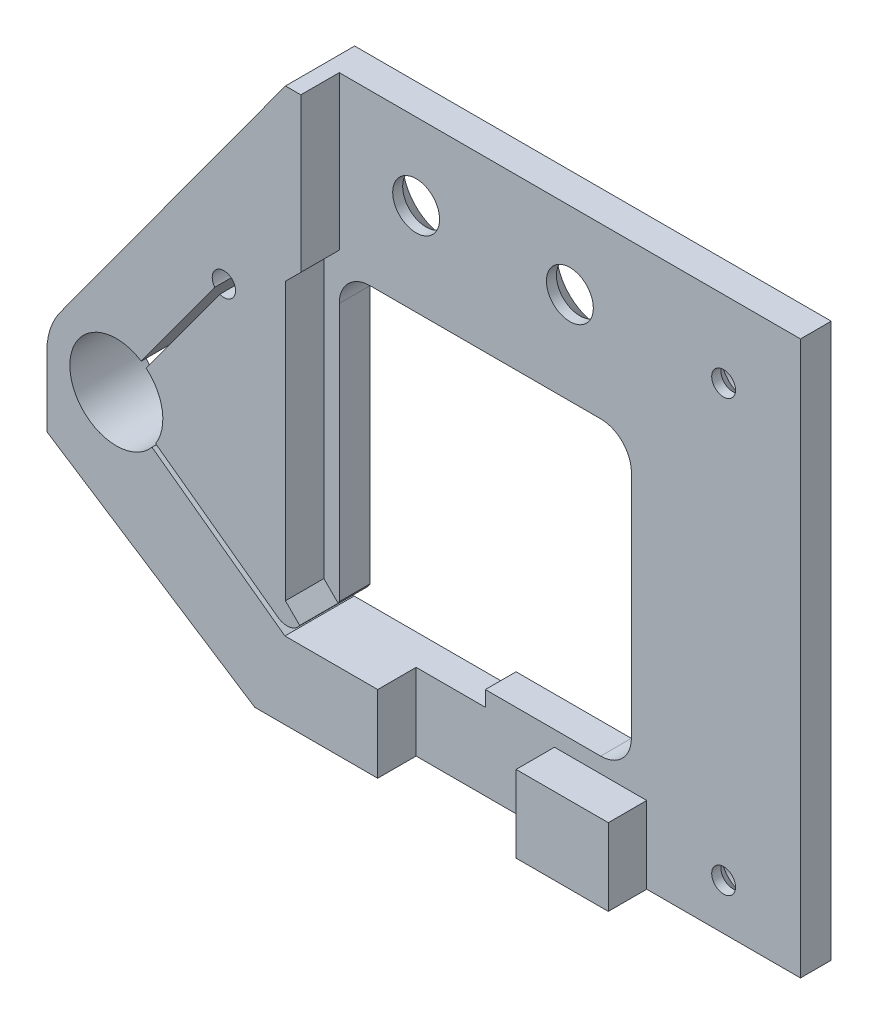
SolidWorks part; units mm, degrees
ref_plane "Front Plane" through (0, 0, 0) normal (0, 0, 1) x (1, 0, 0)
ref_plane "Top Plane" through (0, 0, 0) normal (0, 1, 0) x (1, 0, 0)
ref_plane "Right Plane" through (0, 0, 0) normal (1, 0, 0) x (0, 0, -1)
sketch "Sketch1" plane through (0, 0, 0) normal (0, 0, 1) x (1, 0, 0)
  line L0 (84, 45.5) -> (84, 24)
  line L1 (79, -14.5) -> (24, -14.5) construction
  line L2 (84, 45.5) -> (22, 45.5)
  line L3 (-9.05, 0) -> (-9.05, -8.9672)
  line L4 (22, -16.5) -> (64, -16.5) construction
  line L5 (22, -16.5) -> (22, 25.5) construction
  line L6 (64, -16.5) -> (64, 25.5) construction
  line L7 (22, 25.5) -> (64, 25.5) construction
  line L8 (84, 45.5) -> (24, 45.5) construction
  line L9 (84, -14.5) -> (84, -26.5)
  line L10 (24, 45.5) -> (24, 25.5) construction
  line L11 (24, 45.5) -> (64, 45.5) construction
  line L12 (22, -16.5) -> (64, 25.5) construction
  line L13 (64, -16.5) -> (22, 25.5) construction
  line L14 (43, 23.5) -> (43, 7.5)
  line L15 (64, 45.5) -> (64, 25.5) construction
  line L16 (24, 45.5) -> (64, 25.5) construction
  line L17 (24, 25.5) -> (64, 45.5) construction
  line L18 (24, 23.5) -> (79, 23.5) construction
  line L19 (24, 23.5) -> (24.2, -13.2184)
  line L20 (84, -26.5) -> (18, -26.5)
  line L21 (18, -26.5) -> (-9.05, -8.9672)
  line L22 (22, 45.5) -> (-7.3104, 5.3348)
  line L23 (34, 35.5) -> (54, 35.5) construction
  line L24 (84, -14.5) -> (84, 24)
  line L25 (79, -14.5) -> (79, 23.5) construction
  line L26 (74, -20.5) -> (84, -20.5) construction
  line L27 (0, 0) -> (13.9906, 19.1719) construction
  line L28 (3.8817, 4.6406) -> (13.4512, 17.7542)
  line L29 (3.2354, 5.1122) -> (12.805, 18.2258)
  line L30 (0, 0) -> (7.4321, -5.4235) construction
  line L31 (0.3231, -0.2358) -> (14.3137, 18.9361) construction
  line L32 (-0.3231, 0.2358) -> (13.6675, 19.4077) construction
  line L33 (4.6406, -3.8817) -> (21.932, -16.5)
  line L34 (5.1122, -3.2354) -> (21.0211, -14.8449)
  line L35 (24, -18.0091) -> (24, -14.5) construction
  line L36 (0.2358, 0.3231) -> (7.6679, -5.1004) construction
  line L37 (-0.2358, -0.3231) -> (7.1963, -5.7466) construction
  line L38 (43, -16.5) -> (21.932, -16.5)
  line L39 (24, 23.5) -> (43, 23.5)
  line L40 (43, 1.5) -> (43, -16.5)
  arc A0 (3.2354, 5.1122) -> (4.6406, -3.8817) centre (0, 0) ccw construction
  arc A1 (-7.3104, 5.3348) -> (-9.05, 0) centre (0, 0) ccw
  circle A2 centre (34, 35.5) radius 3.05
  arc A3 (6.3993, -6.3993) -> (-0.7722, -9.017) centre (0, 0) ccw construction
  arc A4 (43, 1.5) -> (43, 7.5) centre (43, 4.5) ccw
  circle A5 centre (54, 35.5) radius 3.05
  circle A6 centre (74, 35.5) radius 1.55
  circle A7 centre (74, -20.5) radius 1.55
  arc A8 (5.1122, -3.2354) -> (3.8817, 4.6406) centre (0, 0) ccw construction
  arc A9 (24.2, -13.2184) -> (21.0211, -14.8449) centre (22.2, -13.2293) cw
  arc A10 (13.4512, 17.7542) -> (12.805, 18.2258) centre (13.9906, 19.1719) ccw
  arc A11 (5.1122, -3.2354) -> (3.8817, 4.6406) centre (0, 0) ccw
  arc A12 (3.2354, 5.1122) -> (4.6406, -3.8817) centre (0, 0) ccw
  point P11 (0, 0)
  point P13 (9.6881, 0)
  point P17 (44, 35.5)
  dimension "D3" = 12.1
  dimension "D4" = 3
  dimension "D1" = 42
  dimension "D2" = 6
  dimension "D6" = 12
  dimension "D12" = 6.1
  dimension "D17" = 3.1
  dimension "D23" = 2
  dimension "D5" = 42
  dimension "D7" = 40
  dimension "D8" = 44
  dimension "D9" = 35.5
  dimension "D10" = 20
  dimension "D11" = 10
  dimension "D13" = 20
  dimension "D14" = 5
  dimension "D15" = 20
  dimension "D16" = 10
  dimension "D22" = 0.2
  dimension "D18" = 0.4
  dimension "D19" = 0.4
  dimension "D20" = 0.4
  dimension "D21" = 0.4
extrude "Boss-Extrude1" add sketch "Sketch1" along normal blind 9
sketch "Sketch2" plane through (0, 0, 9) normal (0, 0, 1) x (1, 0, 0)
  line L0 (24, 25.5) -> (22, 25.5)
  line L1 (22, 25.5) -> (22, -12.5)
  line L2 (64, -16.5) -> (64, -26.5)
  line L3 (26, -16.5) -> (34, -16.5)
  line L4 (22, 25.5) -> (64, -16.5) construction
  line L5 (64, 25.5) -> (22, -16.5) construction
  line L6 (64, -26.5) -> (84, -26.5)
  line L7 (18, -26.5) -> (84, -26.5) construction
  line L8 (43, 4.5) -> (43, -26.5) construction
  line L9 (22, -12.5) -> (26, -16.5)
  line L10 (34, 35.5) -> (54, 35.5) construction
  line L11 (24, 25.5) -> (24, 45.5)
  line L12 (84, -26.5) -> (84, 45.5)
  line L13 (24, 45.5) -> (84, 45.5)
  line L14 (34, -16.5) -> (34, -26.5)
  line L15 (24, 25.5) -> (64, 45.5) construction
  line L16 (24, 45.5) -> (64, 25.5) construction
  line L17 (34, -26.5) -> (52, -26.5)
  line L18 (52, -26.5) -> (52, -16.5)
  line L19 (52, -16.5) -> (64, -16.5)
  point P1 (43, 4.5)
  point P19 (44, 35.5)
  dimension "D1" = 42
  dimension "D3" = 18
  dimension "D2" = 40
extrude "Cut-Extrude1" cut sketch "Sketch2" against normal offset from surface (5 mm away) 4 up to face at (75.55, 35.5, 0)
chamfer "Chamfer2" distance 2.7 angle 45 2 edges at (37.05, 35.5, 0) (57.05, 35.5, 0)
sketch "Sketch3" plane through (0, 0, 4) normal (0, 0, 1) x (1, 0, 0)
  line L1 (24, -14.5) -> (62, -14.5)
  line L2 (24, -14.5) -> (24, 23.5)
  line L3 (24, 23.5) -> (62, 23.5)
  line L4 (62, -14.5) -> (62, 23.5)
  line L5 (24, -14.5) -> (62, 23.5) construction
  line L6 (24, 23.5) -> (62, -14.5) construction
  point P0 (43, 4.5)
  dimension "D1" = 38
extrude "Cut-Extrude2" cut sketch "Sketch3" against normal through all
fillet "Fillet1" radius 4 3 edges at (62, -14.5, 2) (62, 23.5, 2) (24, 23.5, 2)
chamfer "Chamfer3" distance 2 angle 45 1 edges at (22, 25.5, 6.5)
sketch "Sketch4" plane through (0, 0, 0) normal (0, 0, -1) x (-1, 0, 0)
  circle A0 centre (-74, 35.5) radius 3.35
  circle A1 centre (-74, -20.5) radius 3.35
  circle A2 centre (-74, -20.5) radius 1.55 construction
  circle A3 centre (-74, 35.5) radius 1.55 construction
  dimension "D1" = 6.7
extrude "Cut-Extrude3" cut sketch "Sketch4" against normal blind 1
chamfer "Chamfer4" distance 1.8 angle 45 2 edges at (72.45, -20.5, 1) (72.45, 35.5, 1)
